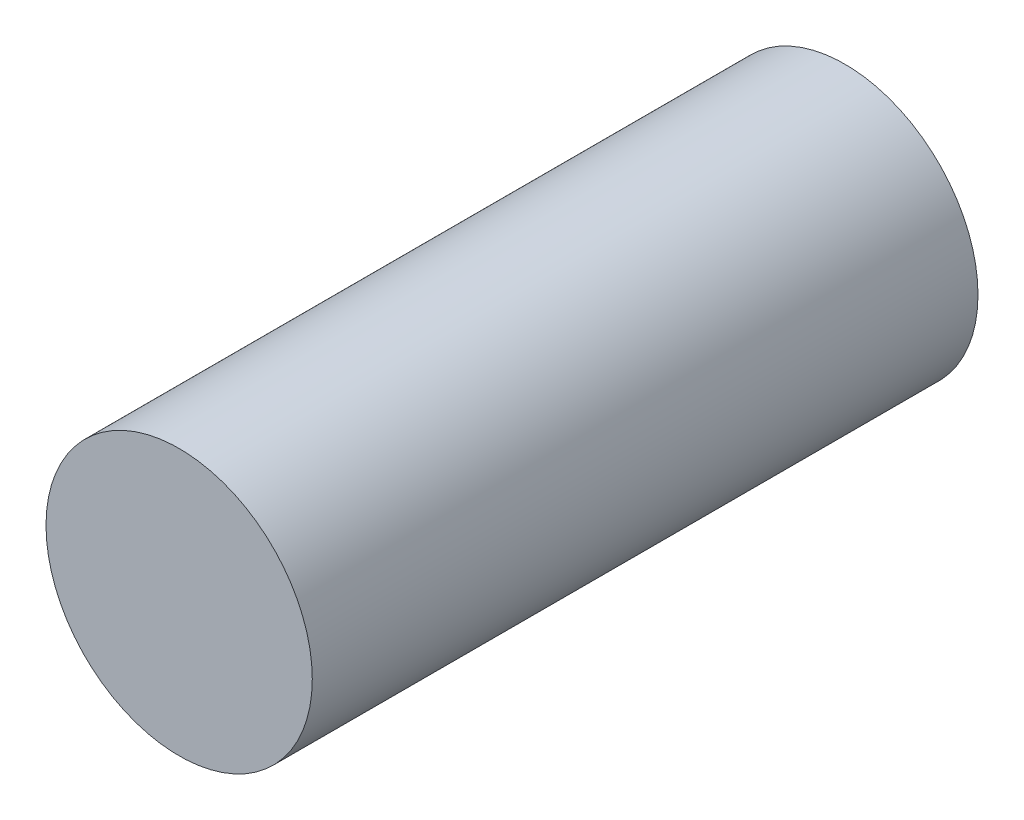
SolidWorks part; units mm, degrees
material "PETG"
ref_plane "Front Plane" through (0, 0, 0) normal (0, 0, 1) x (1, 0, 0)
ref_plane "Top Plane" through (0, 0, 0) normal (0, 1, 0) x (1, 0, 0)
ref_plane "Right Plane" through (0, 0, 0) normal (1, 0, 0) x (0, 0, -1)
sketch "Sketch2" plane through (0, 0, 0) normal (0, 0, 1) x (1, 0, 0)
  circle A0 centre (0, 0) radius 2
  circle A1 centre (0, 0) radius 1.5
  dimension "D1" = 4
  dimension "D2" = 3
extrude "Boss-Extrude1" add sketch "Sketch2" against normal blind 10
extrude "Boss-Extrude2" add sketch "Sketch2<2>" against normal blind 2 contours A1 | A0 A1 region at (-1.9434, 0, 0) region at (0, 0, 0)
sketch "Sketch2<2>" plane through (0, 0, 0) normal (0, 0, 1) x (1, 0, 0) same geometry as "Sketch2"
equation "\"DTailTube\"= 16mm'Диаметр трубки хвостового оперения"
equation "\"FusLenght\"= 700mm"
equation "\"DMotor\"= 35.2mm"
equation "\"MotorArm\"= 320mm"
equation "\"DFus\"= 150mm"
equation "\"DFusTube\"= 30mm'Диаметр трубки внутри фюзеляжа"
equation "\"FusTubeHeight\"= 40mm"
equation "\"FusCentralPartLenght\"= 410mm"
equation "\"FusNoseLenght\"= 150mm"
equation "\"WingOffset\"= 1mm'Расстояние от внутренней поверхности фюзеляжа до профиля крыла по вертикали"
equation "\"EllipseRatio\"= 0.95'Центральная часть фюзеляжа - эллипс. Этот параметр - отношение длин осей эллипса"
equation "\"FrameOffset\"= 0.6mm"
equation "\"DThreadedInsert\"= 3mm'Внешний диамер резьбовых втулок"
equation "\"ThreadedInsertLenght\"=4mm'Длина резьбовых втулок"
equation "\"ThreadedInsertThread\"=2mm'Диаметр резьбы втулки"
equation "\"CenterSectionLenght\"= 140mm'Длина центроплана"
equation "\"b\"= 1700mm'Размах"
equation "\"cwr\"= 236mm'Корневая хорда крыла"
equation "\"TR\"= 0.75'Сужение крыла"
equation "\"cwt\"= \"TR\" * \"cwr\"'Концевая хорда крыла"
equation "\"DWingMainSpar\"= 16mm'Диаметр главного лонжерона крыла"
equation "\"DWingSecondSpar\"= 8mm'Диаметр второго лонжерона крыла"
equation "\"WingSparsDistance\"= 80mm'Расстояния между отверстиями по лонжерон крыла"
equation "\"c\"= 210mm'САХ крыла"
equation "\"FusTubeLenght\"= \"FusLenght\"-90mm'Длина трубки фюзеляжа"
equation "\"bt\"=291mm'Высота лопатки хвоста"
equation "\"ct\"=182mm'Корневая хорда хвоста"
equation "\"lambda_t\"=0.3'Доля хвоста, занатая рулем высоты"
equation "\"TailTubeLenght\"=680mm'Длина хвостовой балки"
equation "\"DStringer\"=6mm'Диаметр стрингеров"
equation "\"TailConnectorBaseLenght\"=20mm'Высота основания конектора хвоста"
equation "\"CargoHolderHoleDistance\"=30mm'Расстояние между крепежными отверстиями для держателя груза"
equation "\"FuselageThickness\"=1.2mm'Толщина фюзеляжа"
equation "\"DTailSpar\"=6mm'Диаметр лонжерона хвостового оперения"
equation "\"TailSparDistance\"=40mm'Расстояние между лонжеронами хвостового оперения"
equation "\"CrossSectionWidth\"=15mm'Ширина кольцевой части шпангоута"
equation "\"HingeLenght\"=30mm'Длина отверстия под шарнир хвостового оперения"
equation "\"HingeWidth\"=2.4mm'Высота отверстия под шарнир ХО"
equation "\"HingeDepth\"=15mm'Глубина отверстия под шарнир ХО"
equation "\"DMagnet\"=3mm'Диаметр магнитов"
equation "\"MagnetHeight\"=2mm'Высота магнитов"
equation "\"D1@Sketch2\"=\"DTailSpar\"-2"
equation "\"D2@Sketch2\"=\"DThreadedInsert\""
